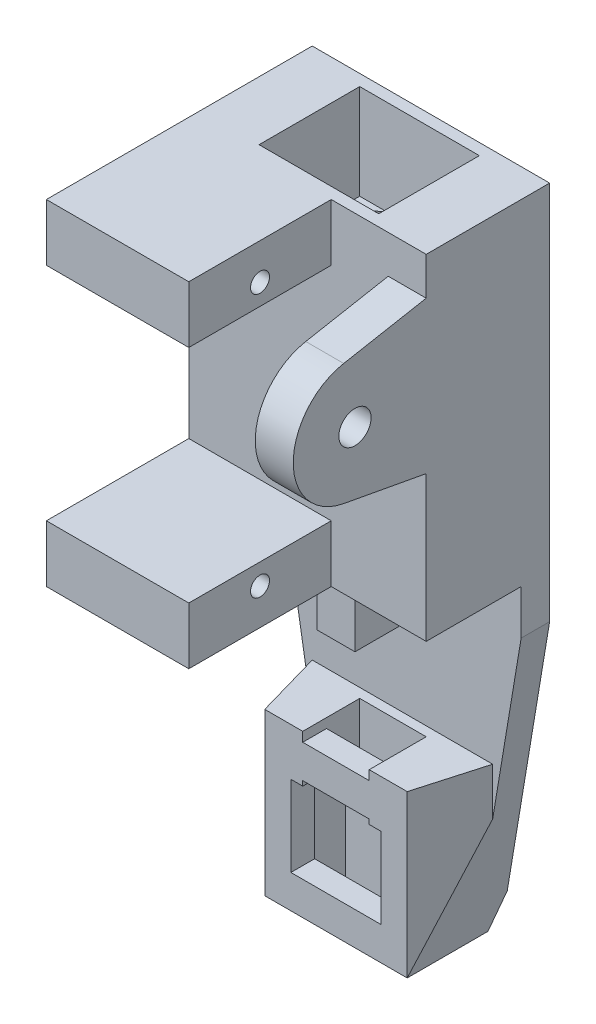
SolidWorks part; units mm, degrees
ref_plane "Plano frontal" through (0, 0, 0) normal (0, 0, 1) x (1, 0, 0)
ref_plane "Plano superior" through (0, 0, 0) normal (0, 1, 0) x (1, 0, 0)
ref_plane "Plano direito" through (0, 0, 0) normal (1, 0, 0) x (0, 0, -1)
sketch "Esboço1" plane through (0, 0, 0) normal (0, 0, 1) x (1, 0, 0)
  line L0 (-12.5, 0) -> (12.5, 0)
  line L1 (12.5, 0) -> (12.5, -40)
  line L2 (12.5, -40) -> (7.5, -70)
  line L3 (7.5, -70) -> (-7.5, -70)
  line L4 (-7.5, -70) -> (-12.5, -40)
  line L5 (-12.5, -40) -> (-12.5, 0)
  point P3 (0, -70)
  point P7 (0, 0)
  dimension "D1" = 40
  dimension "D2" = 30
  dimension "D3" = 25
  dimension "D4" = 15
extrude "Ressalto-extrusão1" add sketch "Esboço1" along normal blind 13
sketch "Esboço2" plane through (0, 0, 13) normal (0, 0, 1) x (1, 0, 0)
  line L1 (2.5, -35.3) -> (-12.5, -35.3)
  line L2 (2.5, -35.3) -> (2.5, -29.3)
  line L3 (2.5, -29.3) -> (-12.5, -29.3)
  line L4 (-12.5, -35.3) -> (-12.5, -29.3)
  line L5 (-12.5, 0) -> (2.5, 0)
  line L6 (-12.5, 0) -> (-12.5, -6)
  line L7 (-12.5, -6) -> (2.5, -6)
  line L8 (2.5, 0) -> (2.5, -6)
  line L11 (12.5, -4) -> (8.5, -4)
  line L12 (12.5, -4) -> (12.5, -20)
  line L13 (12.5, -20) -> (8.5, -20)
  line L14 (8.5, -4) -> (8.5, -20)
  line L15 (-12.5, -6) -> (-12.5, -29.3) construction
  line L16 (-12.5, -28.9) -> (-12.5, -6.4) construction
  point P16 (8.5, -12)
  point P21 (-12.5, -17.65)
  dimension "D1" = 23.3
  dimension "D2" = 6
  dimension "D3" = 15
  dimension "D4" = 21
  dimension "D6" = 22.5
  dimension "D7" = 5.65
  dimension "D8" = 16
  dimension "D9" = 4
extrude "Ressalto-extrusão2" add sketch "Esboço2" along normal blind 15
sketch "Esboço3" plane through (2.5, 0, 0) normal (1, 0, 0) x (0, 0, -1)
  line L0 (-28, -6) -> (-28, -29.3) construction
  line L1 (-28, -17.65) -> (-13, -17.65) construction
  line L2 (-13, -40) -> (-13, -20) construction
  line L3 (-28, -6) -> (-13, -6) construction
  line L4 (-28, 0) -> (-9, 0) construction
  line L5 (-28, 0) -> (-13, 0) construction
  line L6 (-28, -20) -> (-28, -4) construction
  circle A0 centre (-20.5, -3.8) radius 1
  circle A3 centre (-20.5, -31.5) radius 1
  circle A5 centre (-20.5, -12) radius 1.75
  point P24 (-20.5, -6)
  point P31 (-28, -12)
  dimension "D1" = 2
  dimension "D5" = 3.5
  dimension "D2" = 27.7
extrude "Corte-extrusão1" cut sketch "Esboço3" against normal through all contours A5 | A0 | A3 region at (2.5, -3.8, 20.5) region at (2.5, -12, 20.5)
sketch "Esboço10" plane through (12.5, 0, 0) normal (1, 0, 0) x (0, 0, -1)
  line L0 (-28, -20) -> (-28, -4) construction
  line L1 (-20.5, -3.8) -> (-20.5, -31.5) construction
  line L2 (-13, -4) -> (-28, -4)
  line L3 (-28, -4) -> (-28, -20)
  line L4 (-28, -20) -> (-13, -20)
  line L5 (-13, -4) -> (-21.684, -5.6087)
  line L6 (-13, -20) -> (-21.684, -18.3913)
  circle A0 centre (-20.5, -12) radius 1.7
  arc A2 (-21.684, -5.6087) -> (-21.684, -18.3913) centre (-20.5, -12) ccw
  point P5 (-28, -12)
  dimension "D1" = 3.4
  dimension "D2" = 6.5
extrude "Corte-extrusão4" cut sketch "Esboço10" against normal blind 10
sketch "Esboço11" plane through (0, 0, 13) normal (0, 0, 1) x (1, 0, 0)
  line L0 (12.5, -40) -> (12.5, -20) construction
  line L1 (-12.5, -35.3) -> (12.5, -35.3)
  line L2 (-12.5, -35.3) -> (-12.5, -70)
  line L3 (-12.5, -70) -> (12.5, -70)
  line L4 (12.5, -35.3) -> (12.5, -70)
  line L5 (-7.5, -70) -> (7.5, -70) construction
extrude "Corte-extrusão5" cut sketch "Esboço11" against normal blind 10
sketch "Esboço6" plane through (0, -70, 0) normal (0, -1, 0) x (1, 0, 0)
  line L0 (-5, 4) -> (-5, 7.5)
  line L1 (-5, 7.5) -> (-4.75, 7.5)
  line L2 (-4.75, 7.5) -> (-4.75, 10)
  line L3 (-4.75, 10) -> (-7.5, 10)
  line L4 (-7.5, 10) -> (-7.5, 3)
  line L7 (0, 13) -> (0, 11.0668) construction
  line L8 (-7.5, 13) -> (7.5, 13) construction
  line L10 (7.5, 10) -> (7.5, 3)
  line L11 (4.75, 10) -> (7.5, 10)
  line L12 (4.75, 7.5) -> (4.75, 10)
  line L13 (5, 7.5) -> (4.75, 7.5)
  line L14 (5, 4) -> (5, 7.5)
  line L15 (-7.5, 3) -> (7.5, 3)
  line L16 (5, 4) -> (-5, 4)
  point P2 (7.5, 3)
  dimension "D2" = 9.5
  dimension "D3" = 3.5
  dimension "D4" = 1
  dimension "D5" = 6
  dimension "D6" = 10
extrude "Ressalto-extrusão3" add sketch "Esboço6" against normal blind 17
sketch "Esboço7" plane through (0, 0, 3) normal (0, 0, 1) x (1, 0, 0)
  line L0 (-7.5, -70) -> (7.5, -70) construction
  line L1 (2, -38) -> (-2, -38)
  line L2 (2, -38) -> (2, -43)
  line L3 (2, -43) -> (-2, -43)
  line L4 (-2, -38) -> (-2, -43)
  line L5 (2, -38) -> (-2, -43) construction
  line L6 (2, -43) -> (-2, -38) construction
  line L7 (-7.5, -53) -> (-5, -53) construction
  line L8 (5, -53) -> (7.5, -53) construction
  line L9 (7.5, -58) -> (3.5, -58)
  line L10 (7.5, -58) -> (7.5, -53)
  line L11 (7.5, -53) -> (3.5, -53)
  line L12 (3.5, -58) -> (3.5, -53)
  line L13 (7.5, -58) -> (3.5, -53) construction
  line L14 (7.5, -53) -> (3.5, -58) construction
  line L15 (-3.5, -58) -> (-7.5, -58)
  line L16 (-3.5, -58) -> (-3.5, -53)
  line L17 (-3.5, -53) -> (-7.5, -53)
  line L18 (-7.5, -58) -> (-7.5, -53)
  line L19 (-3.5, -58) -> (-7.5, -53) construction
  line L20 (-3.5, -53) -> (-7.5, -58) construction
  line L21 (7.5, -53) -> (7.5, -70) construction
  line L22 (7.5, -53) -> (7.5, -70) construction
  line L23 (-7.5, -53) -> (-7.5, -70) construction
  line L24 (-7.5, -53) -> (-7.5, -70) construction
  point P0 (0, -40.5)
  point P5 (-5.5, -55.5)
  point P8 (0, -70)
  point P11 (5.5, -55.5)
  point P20 (7.5, -53)
  point P29 (-7.617, -53)
  point P30 (-7.5, -53)
  dimension "D1" = 4
  dimension "D2" = 5
  dimension "D3" = 10
  dimension "D4" = 7
  dimension "D5" = 5
  dimension "D6" = 0
extrude "Ressalto-extrusão4" add sketch "Esboço7" along normal up to surface (7 mm away) up to face at (-6.125, -61.5, 10)
sketch "Esboço8" plane through (0, 0, 10) normal (0, 0, 1) x (1, 0, 0)
  line L0 (-7.5, -70) -> (7.5, -70)
  line L1 (7.5, -70) -> (7.5, -66.5)
  line L2 (7.5, -53) -> (7.5, -70) construction
  line L3 (7.5, -66.5) -> (-7.5, -66.5)
  line L4 (-7.5, -53) -> (-7.5, -70) construction
  line L5 (-7.5, -66.5) -> (-7.5, -70)
  line L7 (7.5, -54) -> (-7.5, -54)
  line L8 (7.5, -54) -> (7.5, -57.5)
  line L9 (7.5, -57.5) -> (-7.5, -57.5)
  line L10 (-7.5, -54) -> (-7.5, -57.5)
  dimension "D1" = 3.5
  dimension "D2" = 9
extrude "Ressalto-extrusão5" add sketch "Esboço8" against normal up to surface (2.5 mm away) up to face at (4.875, -64, 7.5)
chamfer "Chanfro2" distance 2 distance2 7 2 edges at (7.5, -61.5, 3) (-7.5, -61.5, 3) first distance on face at (0, -49.575, 3)
chamfer "Chanfro3" distance 1.5 angle 65 1 edges at (0, -70, 0) first distance on face at (0, -70, 5)
sketch "Esboço12" plane through (0, 0, 0) normal (0, 1, 0) x (1, 0, 0)
  line L0 (12.5, -13) -> (12.5, 0) construction
  line L1 (6.3, -11.8) -> (-6.3, -11.8)
  line L2 (6.3, -11.8) -> (6.3, -1.2)
  line L3 (6.3, -1.2) -> (-6.3, -1.2)
  line L4 (-6.3, -11.8) -> (-6.3, -1.2)
  line L5 (6.3, -11.8) -> (-6.3, -1.2) construction
  line L6 (6.3, -1.2) -> (-6.3, -11.8) construction
  point P0 (0, -6.5)
  point P5 (0, 0)
  point P7 (0, 0)
  point P10 (12.5, -6.5)
  dimension "D1" = 10.6
  dimension "D2" = 12.6
extrude "Corte-extrusão6" cut sketch "Esboço12" against normal blind 10
sketch "Esboço13" plane through (0, -10, 0) normal (0, 1, 0) x (1, 0, 0)
  line L0 (-6.3, -1.2) -> (-6.3, -11.8) construction
  line L1 (-6.3, -11.8) -> (6.3, -11.8) construction
  line L2 (-3.4059, -11.8) -> (3.4059, -11.8)
  line L3 (-3.4059, -1.2) -> (3.4059, -1.2)
  line L4 (6.3, -1.2) -> (-6.3, -1.2) construction
  arc A0 (-3.4059, -1.2) -> (-3.4059, -11.8) centre (0, -6.5) ccw
  arc A1 (3.4059, -11.8) -> (3.4059, -1.2) centre (0, -6.5) ccw
  point P2 (-2.6994, -0.8076)
  point P5 (-6.3, -6.5)
  point P8 (0, -11.8)
  dimension "D1" = 12.6
  dimension "D2" = 10.6
extrude "Corte-extrusão7" cut sketch "Esboço13" against normal blind 22
sketch "Esboço15" plane through (-12.5, 0, 0) normal (-1, 0, 0) x (0, 0, 1)
  line L0 (0, 0) -> (0, -40) construction
  line L1 (28, 0) -> (0, 0) construction
  circle A0 centre (6, -28) radius 2
  dimension "D1" = 4
  dimension "D2" = 6
  dimension "D3" = 28
extrude "Corte-extrusão9" cut sketch "Esboço15" against normal blind 15
